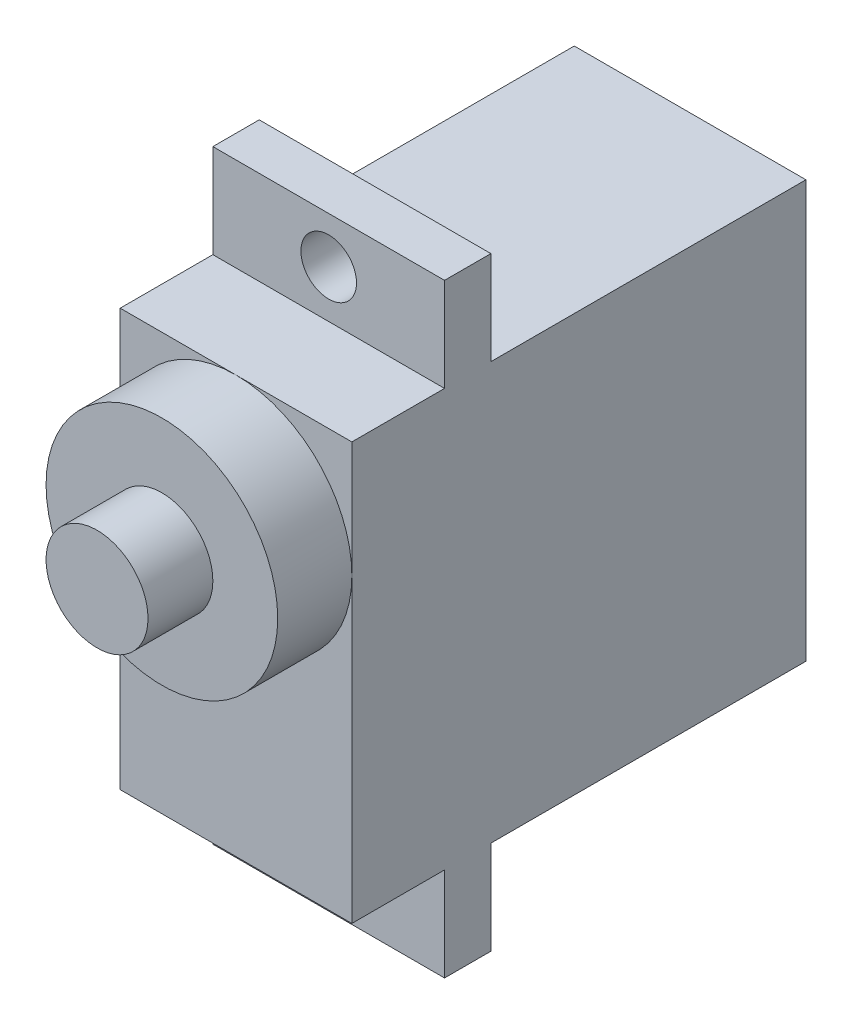
SolidWorks part; units mm, degrees
ref_plane "前视基准面" through (0, 0, 0) normal (0, 0, 1) x (1, 0, 0)
ref_plane "上视基准面" through (0, 0, 0) normal (0, 1, 0) x (1, 0, 0)
ref_plane "右视基准面" through (0, 0, 0) normal (1, 0, 0) x (0, 0, -1)
sketch "草图1" plane through (0, 0, 0) normal (0, 0, 1) x (1, 0, 0)
  line L0 (-1000, 0) -> (49000, 0) construction
  line L1 (-6.25, -11.25) -> (6.25, -11.25)
  line L2 (-6.25, -11.25) -> (-6.25, 11.25)
  line L3 (-6.25, 11.25) -> (6.25, 11.25)
  line L4 (6.25, -11.25) -> (6.25, 11.25)
  line L5 (-6.25, -11.25) -> (6.25, 11.25) construction
  line L6 (-6.25, 11.25) -> (6.25, -11.25) construction
  line L7 (-6.25, -16.3) -> (6.25, -16.3)
  line L8 (-6.25, -16.3) -> (-6.25, 16.3)
  line L9 (-6.25, 16.3) -> (6.25, 16.3)
  line L10 (6.25, -16.3) -> (6.25, 16.3)
  line L11 (-6.25, -16.3) -> (6.25, 16.3) construction
  line L12 (-6.25, 16.3) -> (6.25, -16.3) construction
  circle A0 centre (0, 13.8) radius 1.5
  circle A1 centre (0, -13.8) radius 1.5
  circle A2 centre (0, 5) radius 6.25
  circle A3 centre (0, 5) radius 2.75
  point P0 (0, 0)
  point P6 (0, 0)
  point P15 (0, 16.3)
  dimension "D4" = 3
  dimension "D5" = 2.5
  dimension "D6" = 6.25
  dimension "D7" = 12.5
  dimension "D8" = 5.5
  dimension "D1" = 12.5
  dimension "D2" = 22.5
  dimension "D3" = 32.6
extrude "凸台-拉伸1" add sketch "草图1" along normal blind 24.5 contours A2 L2 L1 L4 | A2 A3 | A3 | A2 L3 L8 | A2 L10 L3 region at (0, -5.4936, 0) region at (-4.854, 9.854, 0) region at (-4.2944, 9.2944, 0) region at (4.854, 9.854, 0) region at (0, 5, 0)
extrude "凸台-拉伸2" add sketch "草图1<3>" along normal blind 19.5 contours L3 L10 L9 L8 A0 | L7 L10 L1 L8 A1 region at (0, -11.3848, 0) region at (-6.1152, 13.775, 0)
sketch "草图1<3>" plane through (0, 0, 0) normal (0, 0, 1) x (1, 0, 0) same geometry as "草图1"
extrude "切除-拉伸1" cut sketch "草图1<4>" along normal blind 17 contours L3 L10 L9 L8 A0 | L7 L10 L1 L8 A1 region at (0, -11.3848, 0) region at (-6.1152, 13.775, 0)
sketch "草图1<4>" plane through (0, 0, 0) normal (0, 0, 1) x (1, 0, 0) same geometry as "草图1"
extrude "凸台-拉伸3" add sketch "草图1<5>" along normal blind 28.5 contours A2 A3 | A3 region at (-4.2944, 9.2944, 0) region at (0, 5, 0)
sketch "草图1<5>" plane through (0, 0, 0) normal (0, 0, 1) x (1, 0, 0) same geometry as "草图1"
extrude "凸台-拉伸4" add sketch "草图1<6>" along normal blind 32 contours A3 region at (0, 5, 0)
sketch "草图1<6>" plane through (0, 0, 0) normal (0, 0, 1) x (1, 0, 0) same geometry as "草图1"
